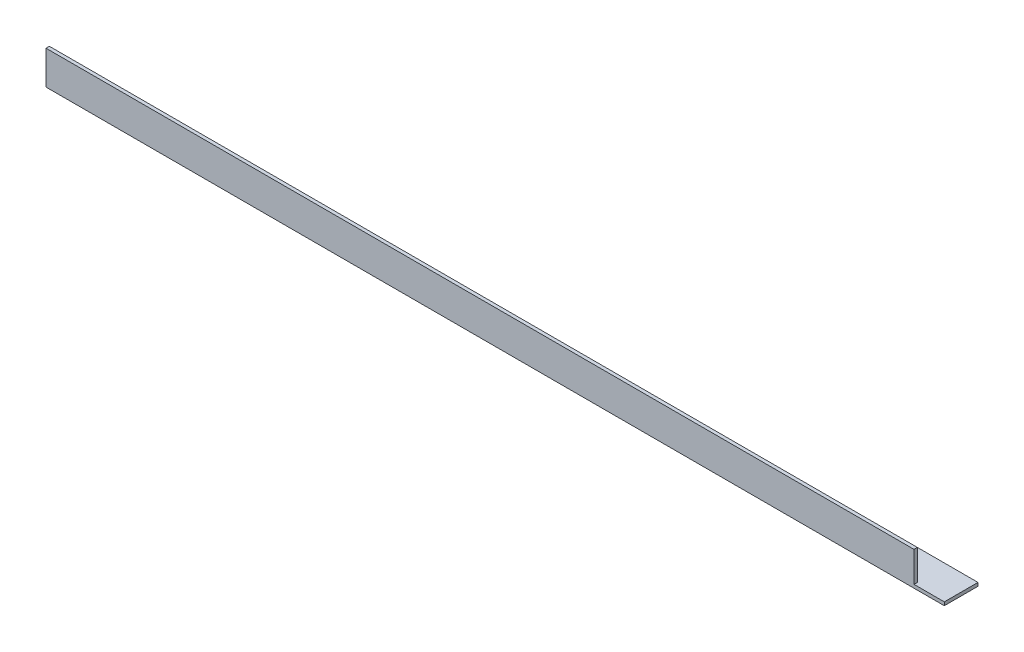
SolidWorks part; units mm, degrees
ref_plane "Спереди" through (0, 0, 0) normal (0, 0, 1) x (1, 0, 0)
ref_plane "Сверху" through (0, 0, 0) normal (0, 1, 0) x (1, 0, 0)
ref_plane "Справа" through (0, 0, 0) normal (1, 0, 0) x (0, 0, -1)
sketch "Эскиз1" plane through (0, 0, 0) normal (1, 0, 0) x (0, 0, -1)
  line L0 (0, 0) -> (30, 0)
  line L1 (0, 0) -> (0, 30)
extrude "Вытянуть-Тонкостенный1" add sketch "Эскиз1" along normal blind 800 thin thin type one direction wall 3
sketch "Эскиз2" plane through (0, 0, 0) normal (0, 0, 1) x (1, 0, 0)
  line L1 (800, 30) -> (773, 30)
  line L2 (800, 30) -> (800, 3)
  line L3 (800, 3) -> (773, 3)
  line L4 (773, 30) -> (773, 3)
extrude "Вырез-Вытянуть1" cut sketch "Эскиз2" against normal up to next
